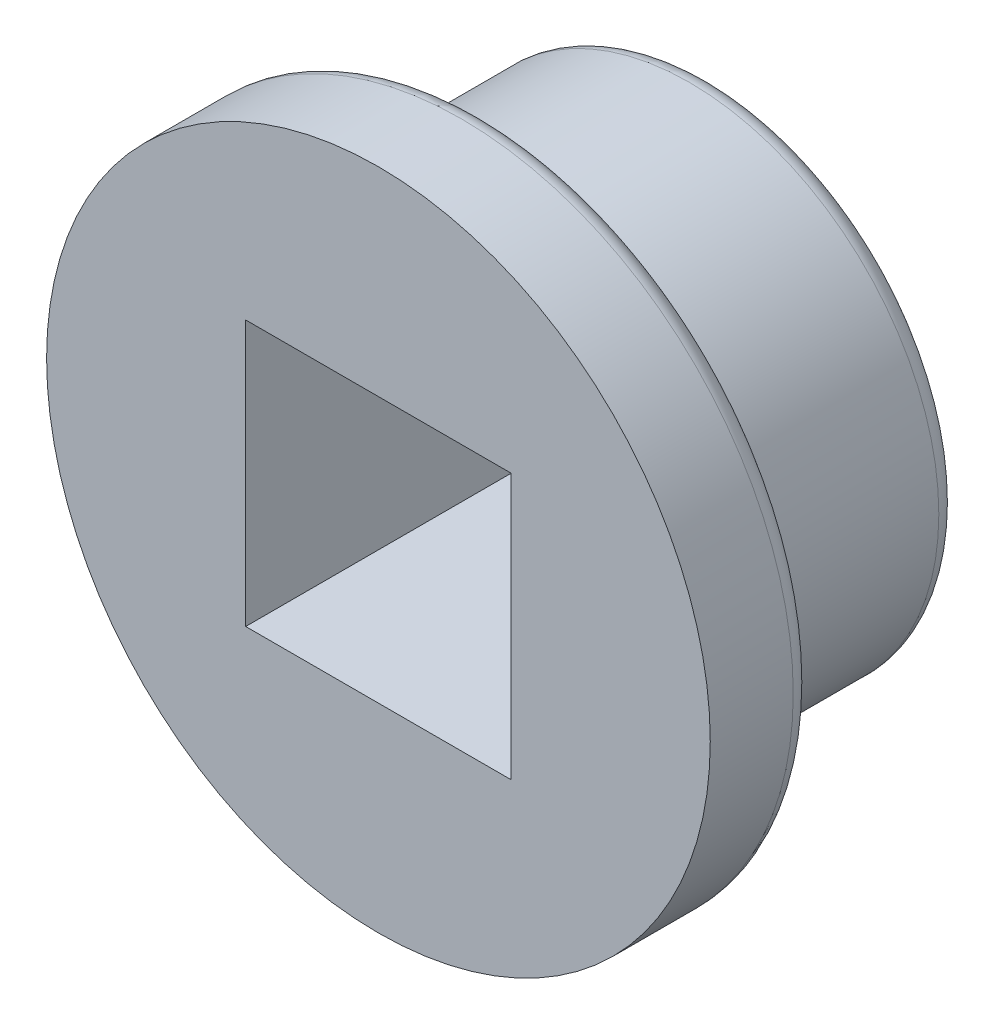
SolidWorks part; units mm, degrees
material "ABS"
ref_plane "Front Plane" through (0, 0, 0) normal (0, 0, 1) x (1, 0, 0)
ref_plane "Top Plane" through (0, 0, 0) normal (0, 1, 0) x (1, 0, 0)
ref_plane "Right Plane" through (0, 0, 0) normal (1, 0, 0) x (0, 0, -1)
sketch "Sketch1" plane through (0, 0, 0) normal (0, 0, 1) x (1, 0, 0)
  line L1 (-3.2, 3.2) -> (3.2, 3.2)
  line L2 (-3.2, 3.2) -> (-3.2, -3.2)
  line L3 (-3.2, -3.2) -> (3.2, -3.2)
  line L4 (3.2, 3.2) -> (3.2, -3.2)
  circle A0 centre (0, 0) radius 6.01
  circle A1 centre (0, 0) radius 8
  point P4 (0, 3.2)
  point P6 (-3.2, 0)
  dimension "D2" = 12.02
  dimension "D3" = 16
  dimension "D1" = 6.4
extrude "Boss-Extrude1" add sketch "Sketch1" against normal blind 5.5 contours A0 L1 L4 L3 L2 region at (-5.84, 0, 0)
extrude "Boss-Extrude2" add sketch "Sketch1<3>" along normal blind 2.5 contours A1 A0 | A0 L1 L4 L3 L2 region at (-5.84, 0, 0) region at (-7.7737, 0, 0)
sketch "Sketch1<3>" plane through (0, 0, 0) normal (0, 0, 1) x (1, 0, 0) same geometry as "Sketch1"
fillet "Fillet1" radius 0.5 2 edges at (8, 0, 0) (6.01, 0, -5.5)
